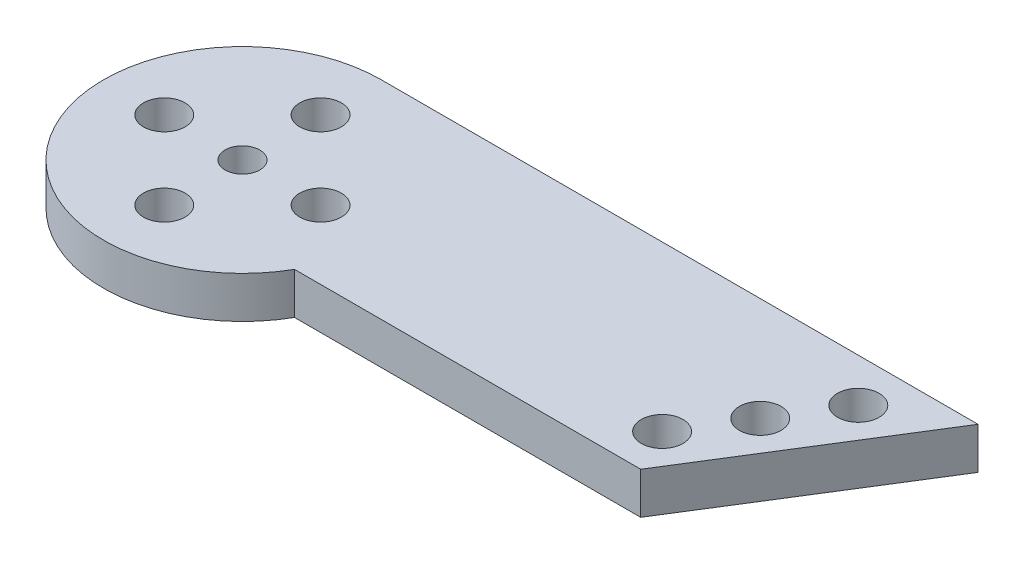
SolidWorks part; units mm, degrees
ref_plane "Front Plane" through (0, 0, 0) normal (0, 0, 1) x (1, 0, 0)
ref_plane "Top Plane" through (0, 0, 0) normal (0, 1, 0) x (1, 0, 0)
ref_plane "Right Plane" through (0, 0, 0) normal (1, 0, 0) x (0, 0, -1)
sketch "Sketch1" plane through (0, 0, 0) normal (0, 1, 0) x (1, 0, 0)
  line L0 (-12.181, 8) -> (22.179, 8)
  line L1 (22.179, 8) -> (12.181, -8)
  line L2 (12.181, -8) -> (-12.181, -8)
  line L3 (13.4414, -1.454) -> (17.7868, 5.5) construction
  line L4 (12.181, -8) -> (-12.181, 8) construction
  line L5 (0, 0) -> (22.179, 8) construction
  arc A0 (-12.181, 8) -> (-12.181, -8) centre (-12.181, 0) ccw
  circle A1 centre (-12.181, 0) radius 4.5 construction
  circle A2 centre (-12.181, 4.5) radius 1.2
  circle A3 centre (-7.681, 0) radius 1.2
  circle A4 centre (-12.181, -4.5) radius 1.2
  circle A5 centre (-16.681, 0) radius 1.2
  circle A6 centre (17.7868, 5.5) radius 1.2
  circle A7 centre (13.4414, -1.454) radius 1.2
  circle A8 centre (15.6141, 2.023) radius 1.2
  circle A9 centre (-12.181, 0) radius 1
  dimension "D1" = 16
  dimension "D2" = 9
  dimension "D3" = 2.4
  dimension "D7" = 2.4
  dimension "D10" = 2
  dimension "D4" = 34.36
  dimension "D5" = 58
  dimension "D6" = 8.2
  dimension "D8" = 2.4
  dimension "D9" = 2.5
extrude "Boss-Extrude1" add sketch "Sketch1" along normal blind 2.4
sketch "Sketch2" plane through (0, 2.4, 0) normal (0, 1, 0) x (1, 0, 0)
  line L0 (14.7093, -3.954) -> (-5.2265, -3.954)
  line L1 (12.181, -8) -> (22.179, 8) construction
  line L3 (-12.181, -8) -> (12.181, -8) construction
  line L4 (-12.181, -8) -> (12.181, -8)
  line L5 (12.181, -8) -> (14.7093, -3.954)
  circle A0 centre (13.4414, -1.454) radius 1.2 construction
  arc A2 (-12.181, -8) -> (-5.2265, -3.954) centre (-12.181, 0) ccw
  point P15 (0, 0)
  point P16 (0, 0)
  dimension "D1" = 2.5
extrude "Cut-Extrude1" cut sketch "Sketch2" against normal through all contours L0 A2 L4 L5
